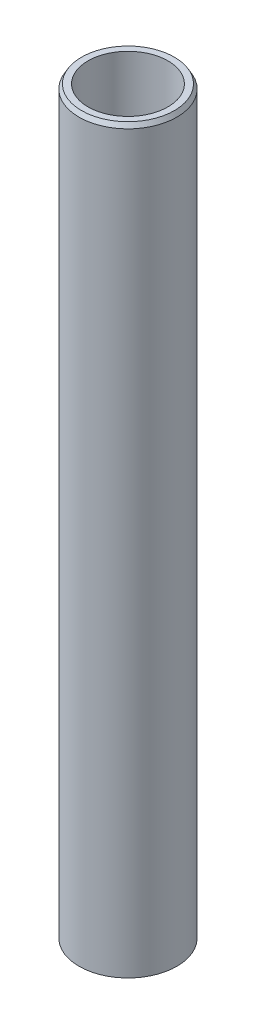
SolidWorks part; units mm, degrees
ref_plane "Front Plane" through (0, 0, 0) normal (0, 0, 1) x (1, 0, 0)
ref_plane "Top Plane" through (0, 0, 0) normal (0, 1, 0) x (1, 0, 0)
ref_plane "Right Plane" through (0, 0, 0) normal (1, 0, 0) x (0, 0, -1)
sketch "Sketch1" plane through (0, 0, 0) normal (0, 1, 0) x (1, 0, 0)
  circle A0 centre (0, 0) radius 27.5
  dimension "SHAFT_OD" = 55
extrude "Boss-Extrude1" add sketch "Sketch1" along normal blind 417.3312
sketch "Sketch2" plane through (0, 0, 0) normal (0, 1, 0) x (1, 0, 0)
  circle A0 centre (0, 0) radius 22.4558
  dimension "BORE_D" = 44.9115
extrude "Cut-Extrude1" cut sketch "Sketch2" along normal through all
chamfer "Chamfer1" distance 2.4734 angle 30 2 edges at (0, 417.3312, 27.5) (0, 0, 27.5) first distance on face at (0, 417.3312, 27.5) first distance on face at (0, 0, 22.4558)
